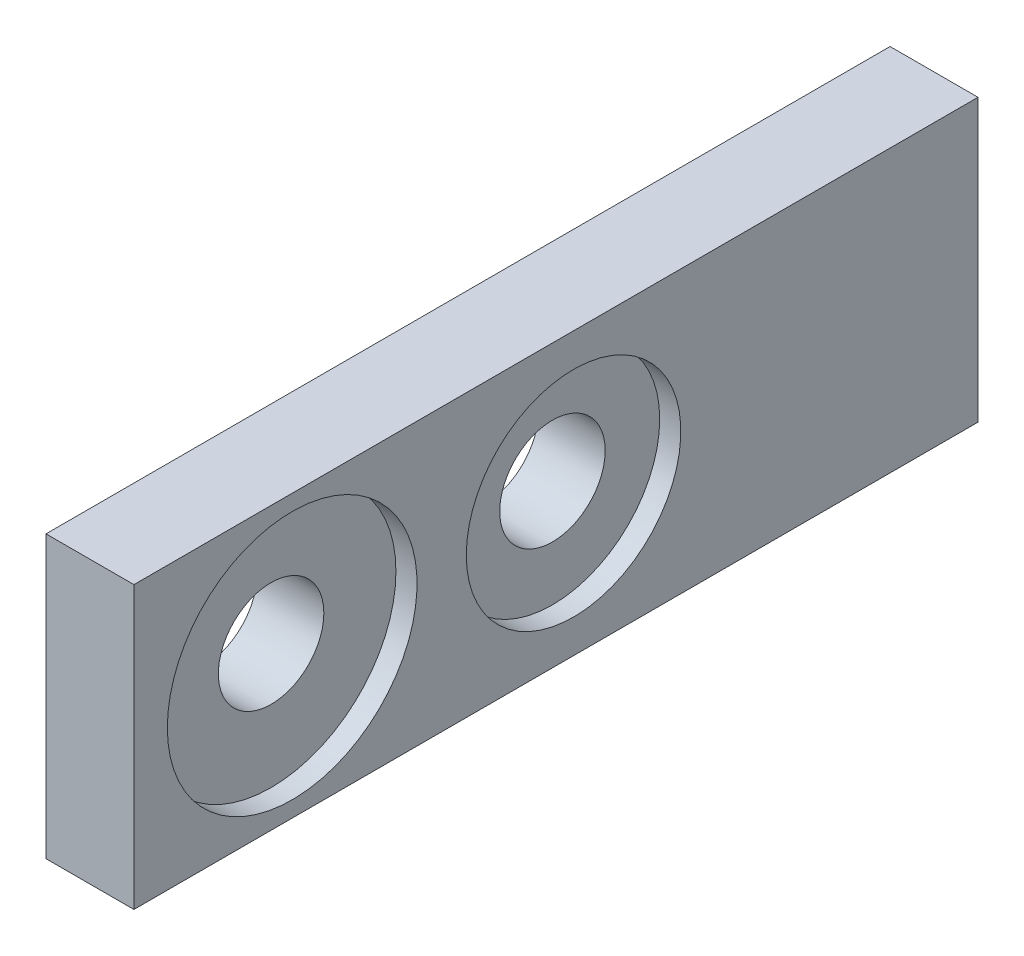
SolidWorks part; units mm, degrees
ref_plane "Front Plane" through (0, 0, 0) normal (0, 0, 1) x (1, 0, 0)
ref_plane "Top Plane" through (0, 0, 0) normal (0, 1, 0) x (1, 0, 0)
ref_plane "Right Plane" through (0, 0, 0) normal (1, 0, 0) x (0, 0, -1)
sketch "Sketch1" plane through (0, 0, 0) normal (0, 0, 1) x (1, 0, 0)
  line L1 (55.6, -8) -> (60.6, -8)
  line L2 (55.6, -8) -> (55.6, 8)
  line L3 (55.6, 8) -> (60.6, 8)
  line L4 (60.6, -8) -> (60.6, 8)
extrude "Boss-Extrude1" add sketch "Sketch1" along normal blind 48 from offset 142
sketch "Sketch2" plane through (0, 0, 0) normal (0, 0, 1) x (1, 0, 0)
  line L1 (55.5, -2.05) -> (58.6, -2.05)
  line L2 (55.5, -2.05) -> (55.5, 2.05)
  line L3 (55.5, 2.05) -> (58.6, 2.05)
  line L4 (58.6, -2.05) -> (58.6, 2.05)
extrude "Boss-Extrude2" add sketch "Sketch2" along normal blind 2.2 from offset 148.9 separate body
combine bodies "Combine1" operation type subtract main body 101 bodies to subtract 102
sketch "Sketch3" plane through (0, 0, 0) normal (0, 1, 0) x (1, 0, 0)
  line L0 (58.8, -149.5) -> (58.8, -150.5)
  line L1 (58.8, -150.5) -> (52.8, -150.5)
  line L2 (52.8, -150.5) -> (52.8, -150.9)
  line L3 (52.8, -150.9) -> (52.2, -150.9)
  line L4 (52.2, -150.9) -> (51.4, -150.1)
  line L5 (51.4, -150.1) -> (51.4, -149.5)
  line L6 (51.4, -149.5) -> (58.8, -149.5)
extrude "Boss-Extrude3" add sketch "Sketch3" along normal blind 3.5 from offset 1.75 offset against normal yes
sketch "Sketch4" plane through (0, 0, 0) normal (1, 0, 0) x (0, 0, -1)
  circle A0 centre (-165, 0) radius 6.1
extrude "Boss-Extrude4" add sketch "Sketch4" along normal blind 1.7 from offset 59.4 separate body
combine bodies "Combine2" operation type subtract main body 104 bodies to subtract 105
sketch "Sketch5" plane through (0, 0, 0) normal (1, 0, 0) x (0, 0, -1)
  circle A0 centre (-165, 0) radius 3
extrude "Boss-Extrude5" add sketch "Sketch5" along normal blind 4.4 from offset 55.1 separate body
combine bodies "Combine3" operation type subtract main body 106 bodies to subtract 107
sketch "Sketch6" plane through (0, 0, 0) normal (1, 0, 0) x (0, 0, -1)
  circle A0 centre (-181, 0) radius 7.1
extrude "Boss-Extrude6" add sketch "Sketch6" along normal blind 1.7 from offset 59.4 separate body
combine bodies "Combine4" operation type subtract main body 108 bodies to subtract 109
sketch "Sketch7" plane through (0, 0, 0) normal (1, 0, 0) x (0, 0, -1)
  circle A0 centre (-181, 0) radius 3
extrude "Boss-Extrude7" add sketch "Sketch7" along normal blind 4.4 from offset 55.1 separate body
combine bodies "Combine5" operation type subtract main body 110 bodies to subtract 111
